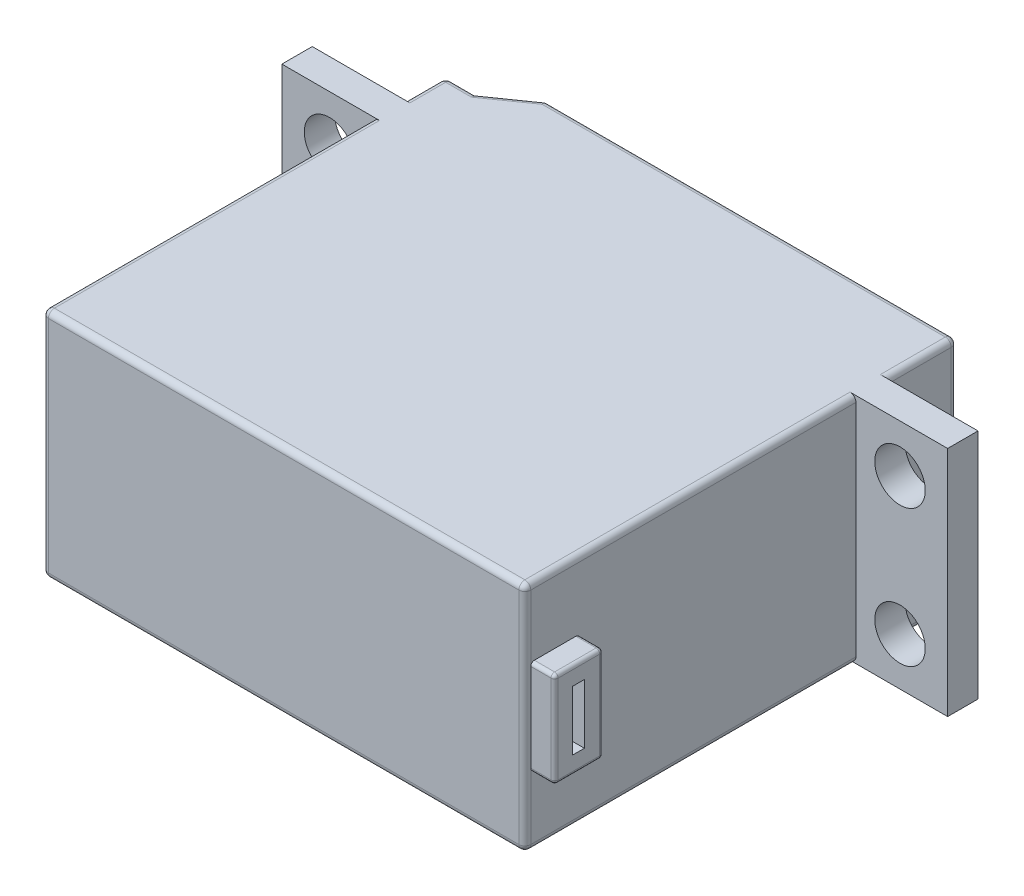
SolidWorks part; units mm, degrees
ref_plane "Plan de face" through (0, 0, 0) normal (0, 0, 1) x (1, 0, 0)
ref_plane "Plan de dessus" through (0, 0, 0) normal (0, 1, 0) x (1, 0, 0)
ref_plane "Plan de droite" through (0, 0, 0) normal (1, 0, 0) x (0, 0, -1)
sketch "Esquisse1" plane through (0, 0, 0) normal (0, 1, 0) x (1, 0, 0)
  line L0 (-25.889, 0) -> (79.3296, 0) construction
  line L1 (0, -14.8446) -> (0, 58.5471) construction
  line L2 (-25.889, 36.3) -> (67.6914, 36.3) construction
  line L3 (40.5, 58.5471) -> (40.5, -14.8446) construction
  line L4 (-15.7265, 27.8) -> (67.6914, 27.8) construction
  line L5 (-15.7265, 30.35) -> (14.0657, 30.35) construction
  line L6 (20.25, 1.9538) -> (20.25, -5.5638) construction
  line L7 (-7.7, 33.6023) -> (-7.7, 17.2676) construction
  line L8 (13.2304, 33.85) -> (-2.733, 33.85) construction
  line L9 (21, 45.018) -> (21, 33.6023) construction
  line L10 (0, 27.8) -> (-7.7, 27.8)
  line L11 (-7.7, 27.8) -> (-7.7, 30.35)
  line L12 (-7.7, 30.35) -> (0, 30.35)
  line L13 (48.2, 27.8) -> (48.2, 30.35)
  line L14 (40.5, 27.8) -> (48.2, 27.8)
  line L15 (48.2, 30.35) -> (40.5, 30.35)
  line L16 (40.5, 27.8) -> (40.5, 0)
  line L17 (40.5, 0) -> (0, 0)
  line L18 (0, 0) -> (0, 27.8)
  line L19 (2.5, 41.6768) -> (2.5, 31.8389) construction
  line L20 (6, 41.6768) -> (6, 31.8389) construction
  line L21 (0, 30.35) -> (0, 33.85)
  line L22 (0, 33.85) -> (2.5, 33.85)
  line L23 (2.5, 33.85) -> (6, 36.3)
  line L24 (6, 36.3) -> (40.5, 36.3)
  line L25 (40.5, 36.3) -> (40.5, 30.35)
  dimension "D1" = 36.3
  dimension "D2" = 40.5
  dimension "D3" = 20.25
  dimension "D4" = 27.8
  dimension "D5" = 2.55
  dimension "D6" = 3.5
  dimension "D7" = 19.5
  dimension "D8" = 2.5
  dimension "D9" = 3.5
  dimension "D10" = 7.7
extrude "Extrusion1" add sketch "Esquisse1" along normal blind 19.5
sketch "Esquisse3" plane through (0, 0, -30.35) normal (0, 0, -1) x (-1, 0, 0)
  line L0 (0, -5.9051) -> (0, 25.0355) construction
  line L1 (-20.25, -5.9051) -> (-20.25, 25.0355) construction
  line L2 (12.0106, 0) -> (-51.1906, 0) construction
  line L3 (-51.1906, 9.75) -> (12.0106, 9.75) construction
  line L4 (11.1658, 4) -> (-6.9445, 4) construction
  line L5 (3.7, -4.8491) -> (3.7, 13.842) construction
  line L6 (7.7, 19.5) -> (7.7, 0) construction
  circle A0 centre (3.7, 4) radius 2.12
  circle A1 centre (3.7, 15.5) radius 2.12
  circle A2 centre (-44.2, 15.5) radius 2.12
  circle A3 centre (-44.2, 4) radius 2.12
  dimension "D1" = 20.25
  dimension "D2" = 9.75
  dimension "D3" = 4
  dimension "D4" = 4
extrude "Enlèv. mat.-Extru.1" cut sketch "Esquisse3" against normal through all
sketch "Esquisse4" plane through (0, 0, -36.3) normal (0, 0, -1) x (-1, 0, 0)
  line L0 (-40.5, -8.0171) -> (-40.5, 24.1379) construction
  line L1 (-52.2994, 9.75) -> (-24.4212, 9.75) construction
  line L2 (-30.75, -8.0171) -> (-30.75, 14.8452) construction
  line L3 (-52.2994, 0) -> (9.4762, 0) construction
  circle A0 centre (-30.75, 9.75) radius 6.8
  dimension "D1" = 9.75
  dimension "D2" = 9.75
extrude "Extrusion2" add sketch "Esquisse4" along normal blind 2
sketch "Esquisse5" plane through (0, 0, -38.3) normal (0, 0, -1) x (-1, 0, 0)
  line L0 (-30.75, 1.3812) -> (-30.75, 12.0996) construction
  line L1 (-21.2532, 9.75) -> (-32.3939, 9.75) construction
  circle A0 centre (-30.75, 9.75) radius 3
extrude "Extrusion3" add sketch "Esquisse5" along normal blind 3.5
chamfer "Chanfrein1" distance 2 angle 45 1 edges at (23.95, 9.75, -38.3)
sketch "Esquisse6" plane through (0, 0, -30.35) normal (0, 0, -1) x (-1, 0, 0)
  line L0 (0, -5.7567) -> (0, 29.5781) construction
  line L1 (12.5532, 0) -> (-6.1576, 0) construction
  line L2 (12.5532, 9.75) -> (-6.6444, 9.75) construction
  line L3 (4, 25.0708) -> (4, 6.6522) construction
  line L4 (-20.25, 29.5781) -> (-20.25, -5.7567) construction
  line L5 (-44.5, 10.5) -> (-40.5, 10.5)
  line L6 (4, 9) -> (0, 9)
  line L7 (4, 9) -> (4, 10.5)
  line L8 (4, 10.5) -> (0, 10.5)
  line L9 (0, 9) -> (0, 10.5)
  line L10 (-40.5, 9) -> (-40.5, 10.5)
  line L11 (-44.5, 9) -> (-40.5, 9)
  line L12 (-44.5, 9) -> (-44.5, 10.5)
  dimension "D1" = 20.25
  dimension "D2" = 9.75
  dimension "D3" = 4
  dimension "D4" = 1.5
  dimension "D5" = 0.75
extrude "Extrusion4" add sketch "Esquisse6" along normal blind 2
chamfer "Chanfrein2" distance 1 angle 60 2 edges at (-4, 9.75, -32.35) (44.5, 9.75, -32.35)
sketch "Esquisse8" plane through (40.5, 0, 0) normal (1, 0, 0) x (0, 0, -1)
  line L0 (0.5872, 21.9631) -> (0.5872, -5.0342) construction
  line L1 (4.5872, -1.7995) -> (4.5872, 21.9631) construction
  line L2 (-2.0747, 9.75) -> (10.8641, 9.75) construction
  line L3 (-5.3508, 0) -> (16.6285, 0) construction
  line L5 (0.5, 13.75) -> (4.5872, 13.75)
  line L6 (0.5, 13.75) -> (0.5, 5.75)
  line L7 (0.5, 5.75) -> (4.5872, 5.75)
  line L8 (4.5872, 13.75) -> (4.5872, 5.75)
  line L9 (2, 12.25) -> (3, 12.25)
  line L10 (2, 12.25) -> (2, 7.25)
  line L11 (2, 7.25) -> (3, 7.25)
  line L12 (3, 12.25) -> (3, 7.25)
  dimension "D1" = 9.75
  dimension "D2" = 4
  dimension "D3" = 8
  dimension "D4" = 4
  dimension "D5" = 1
  dimension "D6" = 5
  dimension "D7" = 1.5
  dimension "D8" = 1.5
extrude "Extrusion5" add sketch "Esquisse8" along normal blind 2
fillet "Congé2" radius 0.5 20 edges at (40.5, 19.5, -13.9) (0, 0, -32.1) (1.25, 0, -33.85) (4.25, 0, -35.075) (23.25, 0, -36.3) (40.5, 0, -33.325) (40.5, 0, -13.9) (20.25, 0, 0) (0, 0, -13.9) (0, 9.75, -33.85) (40.5, 9.75, -36.3) (40.5, 19.5, -33.325) (40.5, 9.75, 0) (0, 9.75, 0) (23.25, 19.5, -36.3) (4.25, 19.5, -35.075) (1.25, 19.5, -33.85) (0, 19.5, -32.1) (0, 19.5, -13.9) (20.25, 19.5, 0)
fillet "Congé3" radius 0.3 8 edges at (42.5, 9.75, -0.5) (42.5, 5.75, -2.5436) (42.5, 9.75, -4.5872) (42.5, 13.75, -2.5436) (41.5, 13.75, -0.5) (41.5, 5.75, -0.5) (41.5, 5.75, -4.5872) (41.5, 13.75, -4.5872)
